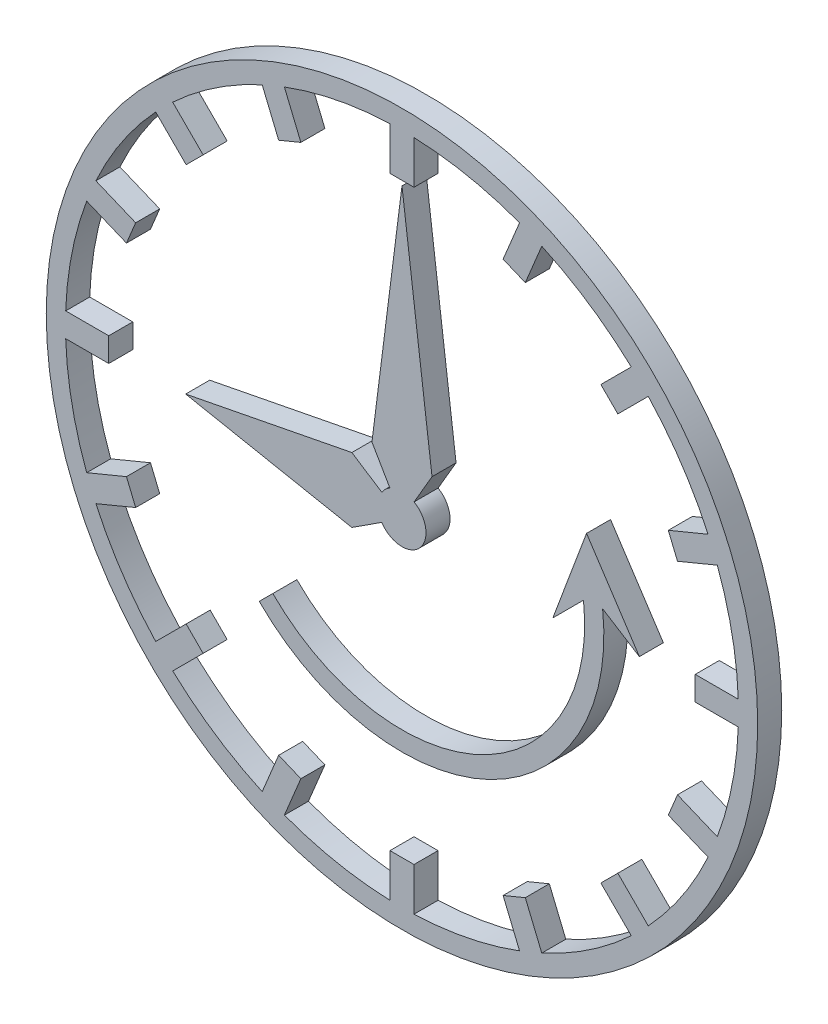
SolidWorks part; units mm, degrees
ref_plane "Front Plane" through (0, 0, 0) normal (0, 0, 1) x (1, 0, 0)
ref_plane "Top Plane" through (0, 0, 0) normal (0, 1, 0) x (1, 0, 0)
ref_plane "Right Plane" through (0, 0, 0) normal (1, 0, 0) x (0, 0, -1)
sketch "Sketch1" plane through (0, 0, 0) normal (0, 0, 1) x (1, 0, 0)
  line L0 (0, 0.6) -> (-0.0625, 0.1073)
  line L1 (-0.0625, 0.1073) -> (0, 0)
  line L2 (0, 0) -> (0.0625, 0.1073)
  line L3 (0.0625, 0.1073) -> (0, 0.6)
  line L4 (0, 0) -> (-0.1043, 0.0675)
  line L5 (-0.1043, 0.0675) -> (-0.45, 0)
  line L6 (-0.45, 0) -> (-0.1043, -0.0675)
  line L7 (-0.1043, -0.0675) -> (0, 0)
  line L8 (0, 0) -> (-0.45, 0) construction
  line L9 (0, 0) -> (0, 0.6) construction
  circle A0 centre (0, 0) radius 0.7
  circle A1 centre (0, 0) radius 0.74
  dimension "D3" = 1.4
  dimension "D1" = 0.6
  dimension "D2" = 0.45
  dimension "D4" = 0.135
  dimension "D5" = 0.125
  dimension "D6" = 0.04
extrude "Boss-Extrude1" add sketch "Sketch1" along normal blind 0.05 contours L2 L3 L0 L1 | L6 L7 L4 L5 | A1 A0 region at (0, 0.2358, 0) region at (-0.1848, 0, 0) region at (-0.7191, 0, 0)
sketch "Sketch2" plane through (0, 0, 0.05) normal (0, 0, 1) x (1, 0, 0)
  circle A0 centre (0, 0) radius 0.05
  dimension "D1" = 0.1
extrude "Boss-Extrude2" add sketch "Sketch2" against normal up to surface (0.05 mm away) up to face at (-0.1646, 0, 0)
sketch "Sketch3" plane through (0, 0, 0.05) normal (0, 0, 1) x (1, 0, 0)
  line L0 (0, -0.0275) -> (0, 0.0275) construction
  line L1 (-0.025, 0.7) -> (0.025, 0.7)
  line L2 (-0.025, 0.7) -> (-0.025, 0.61)
  line L3 (-0.025, 0.61) -> (0.025, 0.61)
  line L4 (0.025, 0.7) -> (0.025, 0.61)
  circle A1 centre (0, 0) radius 0.7 construction
  point P4 (0, 0.7)
  point P8 (0, 0.61)
  point P9 (0.0758, 0.6959)
  dimension "D1" = 0.09
  dimension "D2" = 0.05
extrude "Boss-Extrude3" add sketch "Sketch3" against normal up to surface (0.05 mm away) up to face at (0.7, 0, 0)
ref_axis "Axis1" through (0, 0, -0.0525) along (0, 0, 1)
pattern_circular "CirPattern1" count 16 over 360 about axis through (0, 0, -0.0525) along (0, 0, 1) of "Boss-Extrude3"
sketch "Sketch4" plane through (0, 0, 0.05) normal (0, 0, 1) x (1, 0, 0)
  line L0 (-0.2687, -0.2687) -> (-0.297, -0.297)
  line L1 (0.3776, 0.0424) -> (0.3138, -0.0214)
  line L2 (0.3138, -0.0214) -> (0.3839, 0.1659)
  line L3 (0.3839, 0.1659) -> (0.4938, -0.0012)
  line L4 (0.4938, -0.0012) -> (0.4174, 0.0469)
  line L10 (-0.449, -0.4137) -> (-0.5123, -0.477) construction
  line L11 (0.3839, 0.1659) -> (0.449, -0.4137) construction
  arc A0 (-0.2687, -0.2687) -> (0.3776, 0.0424) centre (0, 0) ccw
  arc A1 (-0.297, -0.297) -> (0.4174, 0.0469) centre (0, 0) ccw
  point P7 (0, 0)
  point P11 (0, 0)
  point P14 (0.449, -0.4137)
  point P15 (0.3835, 0.1688)
  point P16 (0.3175, -0.0177)
  dimension "D2" = 0.38
  dimension "D3" = 0.2
  dimension "D4" = 0.18
  dimension "D1" = 0.04
extrude "Boss-Extrude4" add sketch "Sketch4" against normal up to surface (0.05 mm away) separate body up to face at (-0.0699, 0.086, 0)
